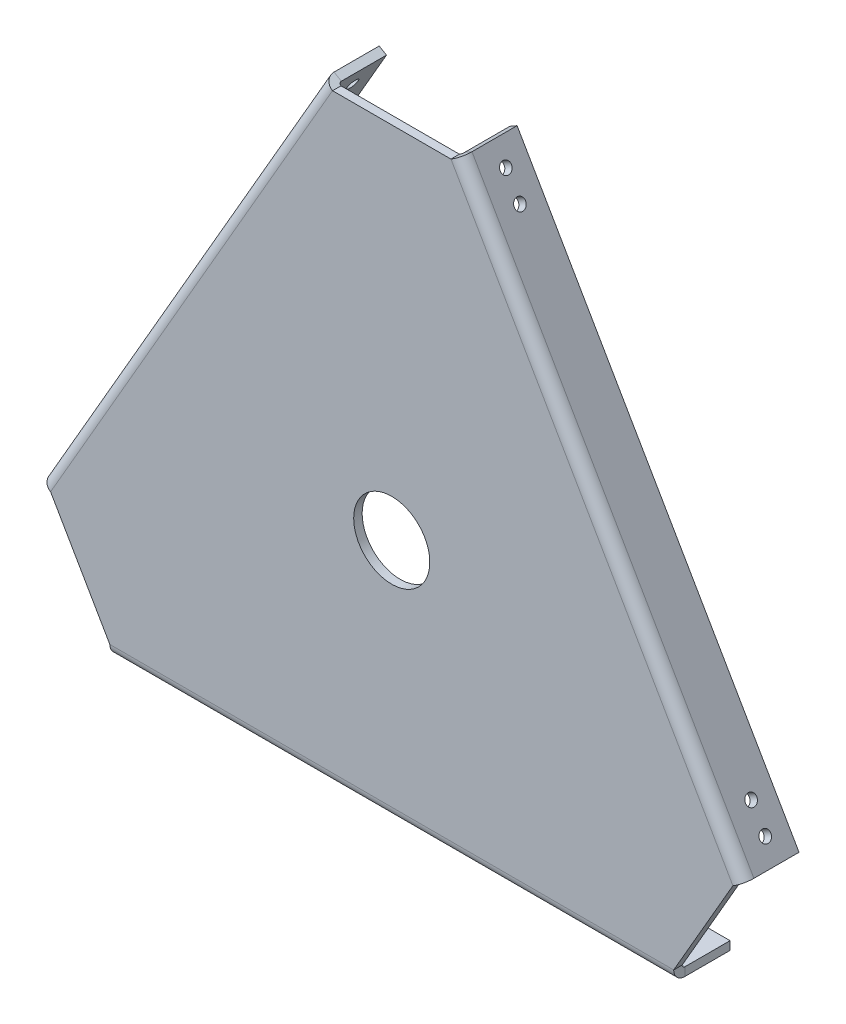
SolidWorks part; units mm, degrees
note: The reader was unsure of these and kept them because the rebuilt part matched: flange length of "Ребро-кромка6".
ref_plane "Спереди" through (0, 0, 0) normal (0, 0, 1) x (1, 0, 0)
ref_plane "Сверху" through (0, 0, 0) normal (0, 1, 0) x (1, 0, 0)
ref_plane "Справа" through (0, 0, 0) normal (1, 0, 0) x (0, 0, -1)
sketch "Эскиз10" plane through (0, 0, 0) normal (0, 0, 1) x (1, 0, 0)
  line L0 (0, 0) -> (-21, 36.3731)
  line L1 (-21, 36.3731) -> (79, 209.5781)
  line L2 (79, 209.5781) -> (121, 209.5781)
  line L3 (121, 209.5781) -> (221, 36.3731)
  line L4 (221, 36.3731) -> (200, 0)
  line L5 (200, 0) -> (0, 0)
  point P6 (130.1748, 221.5138)
  point P8 (0, 39.8568)
  point P9 (0, 39.8568)
  point P10 (129.596, 221.7969)
  point P11 (223.6337, 30.4697)
  point P12 (190.5572, -60.7285)
  dimension "D1" = 200
  dimension "D2" = 42
  dimension "D3" = 60
  dimension "D4" = 60
sheet metal parameters "Листовой металл3" thickness 3 parameters "D1"=0.7366
base flange "Базовая кромка3" sketch "Эскиз10" thickness 3 reverse thickness direction no parameters "D1"=0.7366
edge flange "Ребро-кромка6" sketch "Эскиз39" flange profiles "Эскиз39", "Эскиз40", "Эскиз41" flange angle 90 flange length 20 flange position bend outside bend radius 1 thickness 3 relief rectangular parameters "D6"=10, "D8"=1
sketch "Эскиз39" plane through (-31.5, 18.1865, -3) normal (-0.866, 0.5, 0) x (0.5, 0.866, 0)
  line L0 (221, 0) -> (21, 0) construction
  line L1 (221, 0) -> (21, 0)
  line L2 (21, 0) -> (21, 17)
  line L3 (21, 17) -> (221, 17)
  line L4 (221, 17) -> (221, 0)
sketch "Эскиз40" plane through (181.5, 104.7891, -3) normal (0.866, 0.5, 0) x (0.5, -0.866, 0)
  line L0 (79, 0) -> (-121, 0) construction
  line L1 (79, 0) -> (-121, 0)
  line L2 (-121, 0) -> (-121, 17)
  line L3 (-121, 17) -> (79, 17)
  line L4 (79, 17) -> (79, 0)
sketch "Эскиз41" plane through (0, 0, -3) normal (0, -1, 0) x (-1, 0, 0)
  line L0 (0, 0) -> (-200, 0) construction
  line L1 (0, 0) -> (-200, 0)
  line L2 (-200, 0) -> (-200, 17)
  line L3 (-200, 17) -> (0, 17)
  line L4 (0, 17) -> (0, 0)
bend "EdgeBend10" bend radius 1 bend angle 90 parameters "D5"=9
bend "EdgeBend11" bend radius 1 bend angle 90 parameters "D5"=10
bend "EdgeBend12" bend radius 1 bend angle 90 parameters "D5"=11
sketch "Эскиз47" plane through (-34.9641, 20.1865, 0) normal (-0.866, 0.5, 0) x (0, 0, 1)
  line L0 (-12, 21) -> (-12, 221) construction
  line L1 (-20, 21) -> (-4, 21) construction
  line L2 (-4, 221) -> (-20, 221) construction
  circle A0 centre (-12, 29) radius 2
  circle A1 centre (-12, 39) radius 2
  circle A2 centre (-12, 203) radius 2
  circle A3 centre (-12, 213) radius 2
  point P14 (0, 0)
  point P15 (-12, 203)
  dimension "D1" = 4
  dimension "D4" = 4
  dimension "D2" = 10
  dimension "D3" = 8
  dimension "D5" = 10
  dimension "D6" = 8
extrude "Вырез-Вытянуть4" cut sketch "Эскиз47" against normal up to next normal cut yes
sketch "Эскиз50" plane through (184.9641, 106.7891, 0) normal (0.866, 0.5, 0) x (0, 0, -1)
  line L0 (12, -79) -> (12, 121) construction
  line L1 (4, -79) -> (20, -79) construction
  line L2 (20, 121) -> (4, 121) construction
  circle A0 centre (12, -71) radius 2
  circle A1 centre (12, -61) radius 2
  circle A2 centre (12, 103) radius 2
  circle A3 centre (12, 113) radius 2
  point P10 (0, 0)
  point P13 (0, 0)
  point P16 (0, 0)
  dimension "D3" = 4
  dimension "D1" = 8
  dimension "D2" = 10
  dimension "D4" = 8
  dimension "D5" = 10
extrude "Вырез-Вытянуть6" cut sketch "Эскиз50" against normal up to next normal cut yes
sketch "Эскиз51" plane through (0, -4, 0) normal (0, -1, 0) x (1, 0, 0)
  line L0 (200, -12) -> (0, -12) construction
  line L1 (200, -20) -> (200, -4) construction
  line L2 (0, -4) -> (0, -20) construction
  circle A0 centre (192, -12) radius 2
  circle A1 centre (182, -12) radius 2
  circle A2 centre (18, -12) radius 2
  circle A3 centre (8, -12) radius 2
  point P10 (0, 0)
  point P11 (0, 0)
  point P14 (0, 0)
  point P15 (0, 0)
  dimension "D3" = 4
  dimension "D1" = 10
  dimension "D2" = 8
  dimension "D4" = 10
  dimension "D5" = 8
extrude "Вырез-Вытянуть7" cut sketch "Эскиз51" against normal up to next normal cut yes
sketch "Эскиз52" plane through (0, 0, -3) normal (0, 0, -1) x (-1, 0, 0)
  line L0 (-100, 209.5781) -> (-100, -4) construction
  line L2 (0, -4) -> (-200, -4) construction
  line L3 (-210.5, 18.1865) -> (-28.134, 123.4756) construction
  line L5 (-78.134, 210.0781) -> (21.866, 36.8731) construction
  line L7 (-200, 0) -> (-221, 36.3731) construction
  line L8 (-121, 209.5781) -> (-79, 209.5781) construction
  circle A0 centre (-100, 81.9837) radius 13.5
  point P2 (0, 0)
  point P8 (0, 0)
  point P14 (0, 0)
  point P15 (0, 0)
  dimension "D1" = 27
extrude "Вырез-Вытянуть8" cut sketch "Эскиз52" against normal up to next normal cut yes
flat pattern "Развертка3" [suppressed]
sketch "Сгиб-Линии3" plane through (0, 0, 0) normal (0, 0, 1) x (1, 0, 0)
  line L6 (0, -1.6242) -> (200, -1.6242) construction
  line L7 (222.4066, 37.1852) -> (122.4066, 210.3902) construction
  line L8 (77.5934, 210.3902) -> (-22.4066, 37.1852) construction
  line L9 (0, -1.6242) -> (200, -1.6242) construction
  line L10 (222.4066, 37.1852) -> (122.4066, 210.3902) construction
  line L11 (77.5934, 210.3902) -> (-22.4066, 37.1852) construction
  point P0 (121, 211.2024)
  point P1 (79, 211.2024)
  point P2 (201.4066, -0.8121)
  point P3 (222.4066, 35.561)
  point P4 (-22.4066, 35.561)
  point P5 (-1.4066, -0.8121)
sketch3d "Граничная рамка3" [suppressed]
  line L0 (-63.6504, -24.6242, 0) -> (263.6504, -24.6242, 0) construction
  line L1 (-63.6504, 258.8266, 0) -> (263.6504, 258.8266, 0) construction
  line L2 (-63.6504, -24.6242, 0) -> (-63.6504, 258.8266, 0) construction
  line L3 (263.6504, -24.6242, 0) -> (263.6504, 258.8266, 0) construction
bend of the flat pattern "Плоское состояние-<EdgeBend10>1"
bend of the flat pattern "Плоское состояние-<EdgeBend11>1"
bend of the flat pattern "Плоское состояние-<EdgeBend12>1"
sketch "Эскиз42-1" [suppressed] plane through (0, 211.8266, -3) normal (0, 0, -1) x (1, 0, 0)
  line L0 (100, -1) -> (100, -47) construction
  line L3 (79, -24) -> (121, -24) construction
  circle A0 centre (100, -24) radius 7.5
  circle A1 centre (100, -9) radius 1.5
  circle A2 centre (115, -24) radius 1.5
  circle A3 centre (100, -39) radius 1.5
  circle A4 centre (85, -24) radius 1.5
  dimension "D1" = 15
  dimension "D3" = 3
  dimension "D4" = 15
  dimension "D2" = 15
sketch "Эскиз43-1" [suppressed] plane through (151.9472, -87.7267, -3) normal (0, 0, -1) x (-0.866, 0.5, 0)
  line L0 (-24, 142) -> (-24, 100) construction
  line L1 (-47, 121) -> (-1, 121) construction
  circle A0 centre (-24, 121) radius 7.5
  circle A1 centre (-24, 136) radius 1.5
  circle A2 centre (-9, 121) radius 1.5
  circle A3 centre (-24, 106) radius 1.5
  circle A4 centre (-39, 121) radius 1.5
  dimension "D1" = 15
  dimension "D2" = 3
  dimension "D3" = 15
  dimension "D4" = 15
